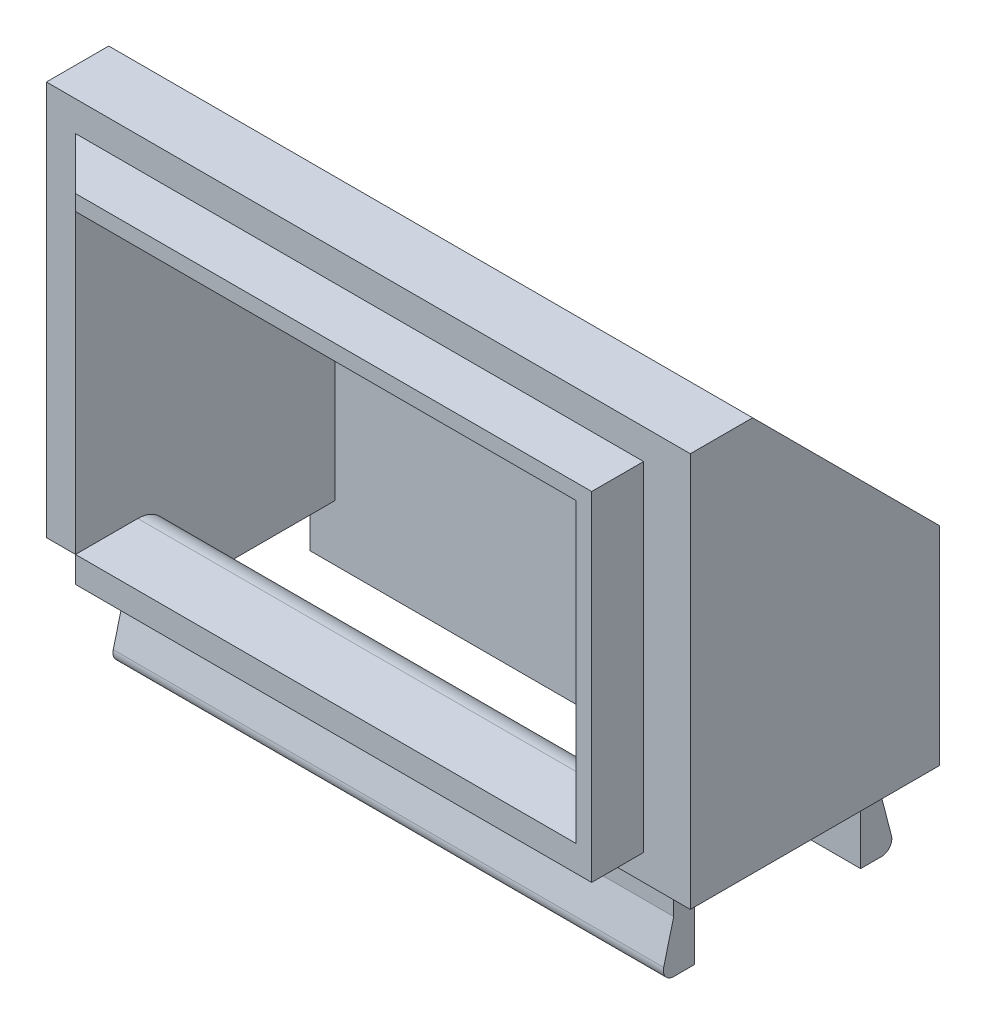
SolidWorks part; units mm, degrees
other "Markup1"
sketch "Sketch16" plane through (15.5, -4.2, 8.5) normal (0.9815, -0.1531, 0.1146) x (0.1118, -0.0263, -0.9934)
ref_plane "Front Plane" through (0, 0, 0) normal (0, 0, 1) x (1, 0, 0)
ref_plane "Top Plane" through (0, 0, 0) normal (0, 1, 0) x (1, 0, 0)
ref_plane "Right Plane" through (0, 0, 0) normal (1, 0, 0) x (0, 0, -1)
sketch "Sketch1" plane through (0, 0, 0) normal (0, 1, 0) x (1, 0, 0)
  line L1 (-15.5, -6) -> (15.5, -6)
  line L2 (-15.5, -6) -> (-15.5, 6)
  line L3 (-15.5, 6) -> (15.5, 6)
  line L4 (15.5, -6) -> (15.5, 6)
  line L5 (-15.5, -6) -> (15.5, 6) construction
  line L6 (-15.5, 6) -> (15.5, -6) construction
  point P0 (0, 0)
  dimension "D1" = 12
  dimension "D2" = 31
extrude "Boss-Extrude1" add sketch "Sketch1" along normal blind 19
sketch "Sketch2" plane through (0, 0, 0) normal (0, -1, 0) x (1, 0, 0)
  line L0 (15.5, 6) -> (15.5, -6) construction
  line L1 (-11.6, 4) -> (12.5, 4)
  line L2 (-11.6, 4) -> (-11.6, -4)
  line L3 (-11.6, -4) -> (12.5, -4)
  line L4 (12.5, 4) -> (12.5, -4)
  line L5 (-15.5, 6) -> (15.5, 6) construction
  line L6 (15.5, -6) -> (-15.5, -6) construction
  line L7 (-15.5, -6) -> (-15.5, 6) construction
  dimension "D1" = 3
  dimension "D2" = 2
  dimension "D3" = 2
  dimension "D4" = 3.9
extrude "Cut-Extrude1" cut sketch "Sketch2" against normal blind 16.8
sketch "Sketch3" plane through (0, 0, 6) normal (0, 0, 1) x (1, 0, 0)
  line L0 (-11.6, 16.8) -> (-11.6, 0) construction
  line L1 (-11.6, 16.8) -> (12.5, 16.8)
  line L2 (-11.6, 16.8) -> (-11.6, 2.5)
  line L3 (-11.6, 2.5) -> (12.5, 2.5)
  line L4 (12.5, 16.8) -> (12.5, 2.5)
  line L5 (12.5, 16.8) -> (12.5, 0) construction
  line L6 (-15.5, 19) -> (15.5, 19) construction
  line L7 (-15.5, 0) -> (15.5, 0) construction
  dimension "D1" = 2.2
  dimension "D2" = 2.5
extrude "Cut-Extrude2" cut sketch "Sketch3" against normal up to surface (2 mm away) up to face at (0.45, 8.4, 4)
fillet "Fillet1" radius 8 1 edges at (0.45, 16.8, -4) profile chamfer
fillet "Fillet2" radius 9 1 edges at (0, 19, -6) profile chamfer
sketch "Sketch6" plane through (0, 0, 0) normal (0, -1, 0) x (1, 0, 0)
  line L1 (12.5, 4) -> (-11.6, 4) construction
  line L3 (12.5, -4) -> (-11.6, -4) construction
  line L8 (-11.6, 4) -> (-11.6, -4) construction
  line L13 (-12.8, 5) -> (13.7, 5)
  line L14 (-12.8, 5) -> (-12.8, 4)
  line L15 (-12.8, 4) -> (13.7, 4)
  line L16 (13.7, 5) -> (13.7, 4)
  line L17 (-12.8, -4) -> (13.7, -4)
  line L18 (-12.8, -4) -> (-12.8, -5)
  line L19 (-12.8, -5) -> (13.7, -5)
  line L20 (13.7, -4) -> (13.7, -5)
  line L21 (12.5, 4) -> (12.5, -4) construction
  dimension "D1" = 1.2
  dimension "D2" = 1.2
  dimension "D3" = 1
  dimension "D4" = 1
extrude "Boss-Extrude3" add sketch "Sketch6" along normal blind 4.2
sketch "Sketch14" plane through (13.7, 0, 0) normal (1, 0, 0) x (0, 0, -1)
  line L2 (5.4841, -3.575) -> (5, -1.7)
  line L5 (5, -4.2) -> (5, 0) construction
  line L8 (-5, -4.2) -> (-5, -1.7)
  line L10 (5, -4.2) -> (5, -1.7)
  line L17 (-5, -4.2) -> (-5, 0) construction
  line L18 (-5.4841, -3.575) -> (-5, -1.7)
  arc A0 (5, -4.2) -> (5.4841, -3.575) centre (5, -3.7) ccw
  arc A1 (-5.4841, -3.575) -> (-5, -4.2) centre (-5, -3.7) ccw
  dimension "D3" = 1
  dimension "D1" = 1
  dimension "D4" = 2.5
extrude "Boss-Extrude6" add sketch "Sketch14" against normal up to surface (26.5 mm away) up to face at (-12.8, -2.1, 4.5)
sketch "Sketch15" plane through (0, 0, 0) normal (0, -1, 0) x (1, 0, 0)
  line L1 (-11.6, 4) -> (-12.8, 4)
  line L2 (-11.6, 4) -> (-11.6, -4)
  line L3 (-11.6, -4) -> (-12.8, -4)
  line L4 (-12.8, 4) -> (-12.8, -4)
  line L5 (12.5, -4) -> (13.7, -4)
  line L6 (12.5, -4) -> (12.5, 4)
  line L7 (12.5, 4) -> (13.7, 4)
  line L8 (13.7, -4) -> (13.7, 4)
  line L9 (-11.6, 4) -> (-11.6, -4) construction
  line L12 (12.5, -4) -> (12.5, 4) construction
  point P12 (-11.6, 0)
  point P17 (12.5, 0)
  dimension "D1" = 1.2
  dimension "D2" = 1.2
  dimension "D3" = 8
  dimension "D4" = 8
extrude "Boss-Extrude7" add sketch "Sketch15" along normal blind 1.5
sketch "Sketch4" plane through (0, 0, 6) normal (0, 0, 1) x (1, 0, 0)
  line L0 (-11.6, 2.5) -> (12.5, 2.5) construction
  line L1 (12.5, 2.5) -> (12.5, 16.8) construction
  line L2 (12.5, 16.8) -> (-11.6, 16.8) construction
  line L3 (-11.6, 16.8) -> (-11.6, 2.5) construction
  line L4 (-11.6, 2.5) -> (12.5, 2.5)
  line L5 (12.5, 2.5) -> (12.5, 16.8)
  line L6 (12.5, 16.8) -> (-11.6, 16.8)
  line L7 (-11.6, 16.8) -> (-11.6, 2.5)
  line L9 (-14.1, 17.55) -> (13.25, 17.55)
  line L10 (-14.1, 17.55) -> (-14.1, 1.25)
  line L11 (-14.1, 1.25) -> (13.25, 1.25)
  line L12 (13.25, 17.55) -> (13.25, 1.25)
  dimension "D1" = 2.5
  dimension "D2" = 0.75
  dimension "D3" = 14.3
  dimension "D4" = 0.75
  dimension "D5" = 1.25
extrude "Boss-Extrude2" add sketch "Sketch4" along normal blind 2.5
chamfer "Chamfer1" distance 2.5 angle 45 1 edges at (-14.1, 9.4, 8.5)
fillet "Fillet3" radius 1.5 1 edges at (0.45, 2.5, 4)
sketch "Sketch12" plane through (0, 0, 8.5) normal (0, 0, 1) x (1, 0, 0)
  line L0 (5.25, 17.55) -> (5.25, 16.8)
  line L1 (5.25, 2.5) -> (5.25, 1.25)
  line L8 (13.25, 17.55) -> (-11.6, 17.55)
  line L9 (-11.6, 17.55) -> (-11.6, 16.8)
  line L10 (-11.6, 16.8) -> (12.5, 16.8)
  line L11 (12.5, 16.8) -> (12.5, 2.5)
  line L12 (12.5, 2.5) -> (-11.6, 2.5)
  line L13 (-11.6, 2.5) -> (-11.6, 1.25)
  line L14 (-11.6, 1.25) -> (13.25, 1.25)
  line L15 (13.25, 1.25) -> (13.25, 17.55)
  line L16 (13.25, 17.55) -> (-11.6, 17.55)
  line L17 (-11.6, 17.55) -> (-11.6, 16.8)
  line L18 (-11.6, 16.8) -> (12.5, 16.8)
  line L19 (12.5, 16.8) -> (12.5, 2.5)
  line L20 (12.5, 2.5) -> (-11.6, 2.5)
  line L21 (-11.6, 2.5) -> (-11.6, 1.25)
  line L22 (-11.6, 1.25) -> (13.25, 1.25)
  line L23 (13.25, 1.25) -> (13.25, 17.55)
  line M10 (13.25, 17.55) -> (-11.6, 17.55)
  line M12 (-11.6, 16.8) -> (12.5, 16.8)
  line M13 (12.5, 16.8) -> (12.5, 2.5)
  line M14 (12.5, 2.5) -> (-11.6, 2.5)
  line M16 (-11.6, 1.25) -> (13.25, 1.25)
  line M17 (13.25, 1.25) -> (13.25, 17.55)
  dimension "D2" = 8
  dimension "D1" = 0
extrude "Boss-Extrude5" [suppressed] add sketch "Sketch12" along normal blind 8 contours L1 L0 M14 M16 M17 M10 M12 M13
chamfer "Chamfer2" [suppressed] distance 8 angle 45
